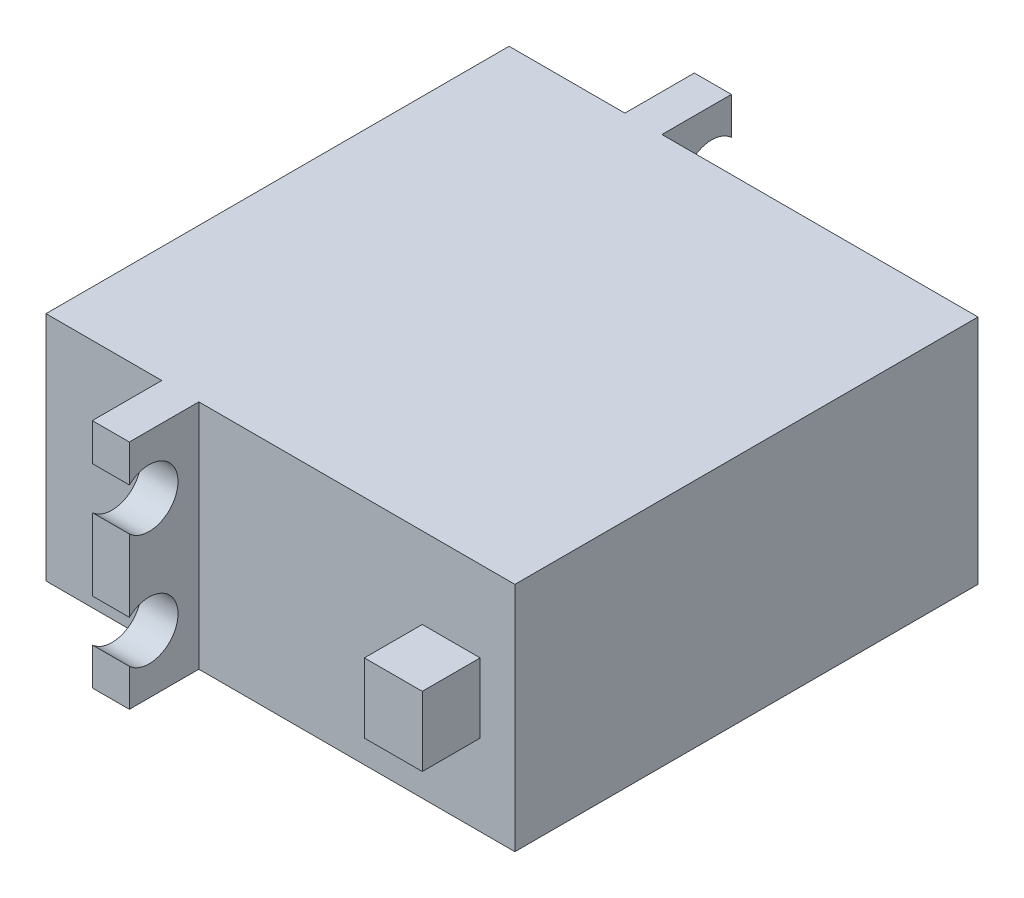
SolidWorks part; units mm, degrees
ref_plane "Front Plane" through (0, 0, 0) normal (0, 0, 1) x (1, 0, 0)
ref_plane "Top Plane" through (0, 0, 0) normal (0, 1, 0) x (1, 0, 0)
ref_plane "Right Plane" through (0, 0, 0) normal (1, 0, 0) x (0, 0, -1)
sketch "Sketch1" plane through (0, 0, 0) normal (0, 1, 0) x (1, 0, 0)
  line L0 (-20.25, -10.2) -> (-25.75, -10.2) construction
  line L1 (-20.25, -20) -> (20.25, -20)
  line L2 (-20.25, -20) -> (-20.25, 20)
  line L3 (-20.25, 20) -> (20.25, 20)
  line L4 (20.25, -20) -> (20.25, 20)
  line L5 (-20.25, -20) -> (20.25, 20) construction
  line L6 (-20.25, 20) -> (20.25, -20) construction
  line L7 (-20.25, -13.2) -> (-25.75, -13.2)
  line L8 (-25.75, -13.2) -> (-25.75, -7.2)
  line L9 (-25.75, -7.2) -> (-20.25, -7.2)
  line L10 (-10.25, 20) -> (-10.25, 24.2331)
  line L11 (-10.25, 24.2331) -> (-7.05, 24.2331)
  line L12 (-7.05, 24.2331) -> (-7.05, 20)
  line L13 (-10.25, -20) -> (-10.25, -24.2331)
  line L14 (-10.25, -24.2331) -> (-7.05, -24.2331)
  line L15 (-7.05, -24.2331) -> (-7.05, -20)
  line L16 (-20.25, -10.2) -> (20.25, -10.2) construction
  point P0 (0, 0)
  dimension "D1" = 40
  dimension "D2" = 40.5
  dimension "D3" = 46
  dimension "D4" = 6
  dimension "D5" = 9.8
  dimension "D6" = 3.2
  dimension "D7" = 27.3
sketch "Sketch2" plane through (0, 0, 0) normal (1, 0, 0) x (0, 0, -1)
  line L1 (-20, -10) -> (20, -10)
  line L2 (-20, -10) -> (-20, 10)
  line L3 (-20, 10) -> (20, 10)
  line L4 (20, -10) -> (20, 10)
  line L5 (-20, -10) -> (20, 10) construction
  line L6 (-20, 10) -> (20, -10) construction
  line L7 (-26, 0) -> (26, 0) construction
  line L8 (-20, 10) -> (-26, 10)
  line L9 (-26, 10) -> (-26, -10)
  line L10 (-26, -10) -> (-20, -10)
  line L11 (20, 10) -> (26, 10)
  line L12 (26, 10) -> (26, -10)
  line L13 (26, -10) -> (20, -10)
  line L14 (0, 0) -> (0, 8.0962) construction
  circle A0 centre (-24.3, 4.95) radius 2.5
  circle A1 centre (-24.3, -4.95) radius 2.5
  circle A2 centre (24.3, 4.95) radius 2.5
  circle A3 centre (24.3, -4.95) radius 2.5
  circle A4 centre (-10.2, 0) radius 3
  dimension "D5" = 5
  dimension "D7" = 6
  dimension "D1" = 40
  dimension "D2" = 20
  dimension "D3" = 9.9
  dimension "D4" = 48.6
  dimension "D6" = 52
extrude "Boss-Extrude1" add sketch "Sketch2" against normal up to vertex (20.25 mm away) from vertex contours L1 L4 L3 L2 A4 | A4 region at (0, 0, -0.3737) region at (0, 0, 10.2) up to point (-20.25, 0, 20) starting at point (20.25, 0, 20)
extrude "Boss-Extrude2" add sketch "Sketch2<3>" against normal up to vertex (10.25 mm away) from vertex contours A1 L9 L10 L2 L8 A0 | L12 A3 A2 L11 L4 L13 region at (0, 0, 22.5569) region at (0, 0, -22.5569) up to point (-10.25, 0, 24.2331) starting at point (-7.05, 0, 24.2331)
sketch "Sketch2<3>" plane through (0, 0, 0) normal (1, 0, 0) x (0, 0, -1) same geometry as "Sketch2"
extrude "Boss-Extrude3" add sketch "Sketch2<5>" against normal up to vertex (25.75 mm away) from vertex contours A4 up to point (-25.75, 0, 13.2) starting at point (-20.25, 0, 20)
sketch "Sketch2<5>" plane through (0, 0, 0) normal (1, 0, 0) x (0, 0, -1) same geometry as "Sketch2"
sketch "Sketch3" plane through (0, 0, 20) normal (0, 0, 1) x (1, 0, 0)
  line L0 (0, 0) -> (20.25, 0) construction
  line L1 (20.25, -10) -> (20.25, 10) construction
  line L3 (12.25, 3) -> (17.25, 3)
  line L4 (12.25, 3) -> (12.25, -3)
  line L5 (12.25, -3) -> (17.25, -3)
  line L6 (17.25, 3) -> (17.25, -3)
  point P9 (11.628, 3.7149)
  dimension "D1" = 5
  dimension "D2" = 3
  dimension "D3" = 6
extrude "Boss-Extrude4" add sketch "Sketch3" along normal blind 5
